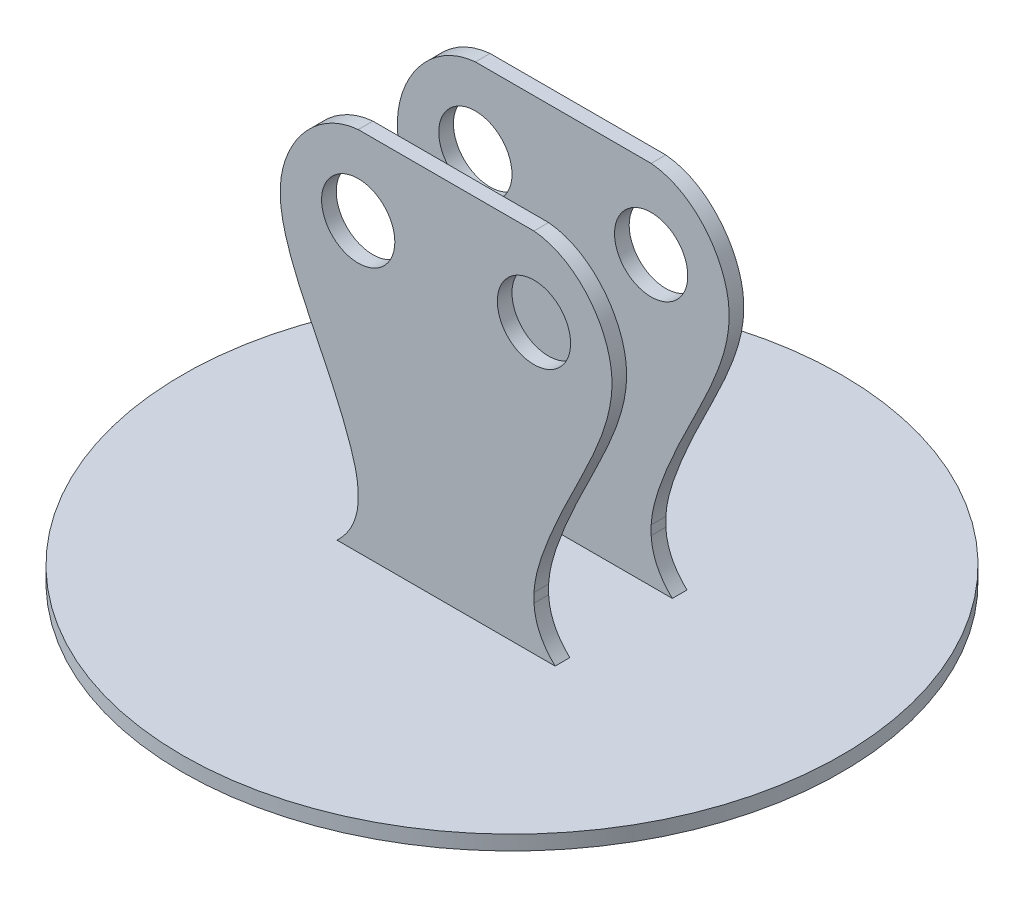
SolidWorks part; units mm, degrees
material "AISI 1020 Steel, Cold Rolled"
ref_plane "Front Plane" through (0, 0, 0) normal (0, 0, 1) x (1, 0, 0)
ref_plane "Top Plane" through (0, 0, 0) normal (0, 1, 0) x (1, 0, 0)
ref_plane "Right Plane" through (0, 0, 0) normal (1, 0, 0) x (0, 0, -1)
sketch "Sketch1" plane through (0, 0, 0) normal (0, 1, 0) x (1, 0, 0)
  circle A0 centre (0, 0) radius 45
extrude "Boss-Extrude1" add sketch "Sketch1" along normal blind 2
sketch "Sketch2" plane through (0, 2, 0) normal (0, 1, 0) x (1, 0, 0)
  line L0 (0, 0) -> (0, -7)
  line L2 (0, -7) -> (-12, -7)
  line L3 (0, -7) -> (0, -9)
  line L4 (0, -9) -> (-12, -9)
  line L5 (-12, -7) -> (-12, -9)
  dimension "D1" = 7
  dimension "D2" = 2
  dimension "D3" = 12
extrude "Boss-Extrude2" add sketch "Sketch2" along normal blind 50 contours L2 L5 L4 L3 region at (-6, 2, 8)
sketch "Sketch3" plane through (0, 0, 9) normal (0, 0, 1) x (1, 0, 0)
  line L0 (-12, 52) -> (-12, 2) construction
  line L1 (45, 2) -> (-45, 2) construction
  line L2 (-12, 2) -> (-14.891, 2)
  line L7 (-12, 2) -> (0, 2)
  line L8 (0, 2) -> (0, 52)
  line L9 (0, 52) -> (-12, 52)
  line L10 (-12, 52) -> (-12, 2)
  line L14 (-12, 52) -> (-12, 2)
  spline S0 degree 3 poles (-12, 52) (-17.7076, 51.5001) (-24.2529, 43.2597) (-21.3975, 31.9625) (-17.3388, 23.9745) (-12.6521, 14.2022) (-10.6555, 6.0131) (-14.891, 2) knots 0 0 0 0 0.28798 0.430456 0.586456 0.756217 1 1 1 1
  line M10 (-12, 52) -> (-12, 2)
  dimension "D1" = 0
extrude "Boss-Extrude3" add sketch "Sketch3" against normal up to surface (2 mm away) contours S0 M10 | S0 L2 M10 region at (-12.8452, 3.5339, 9) region at (-16.1263, 35.5518, 9) up to face at (-6, 27, 7)
sketch "Sketch4" plane through (0, 0, 9) normal (0, 0, 1) x (1, 0, 0)
  line L0 (0, 41.2016) -> (-12, 41.2016)
  line L1 (0, 52) -> (0, 2) construction
  circle A0 centre (-12, 41.2016) radius 5
extrude "Cut-Extrude1" cut sketch "Sketch4" against normal blind 50 contours A0
mirror "Mirror1" about plane through (0, 52, 0) normal (1, 0, 0) of bodies 104
mirror "Mirror2" about plane through (0, 0, 0) normal (0, 0, 1) of bodies 105
